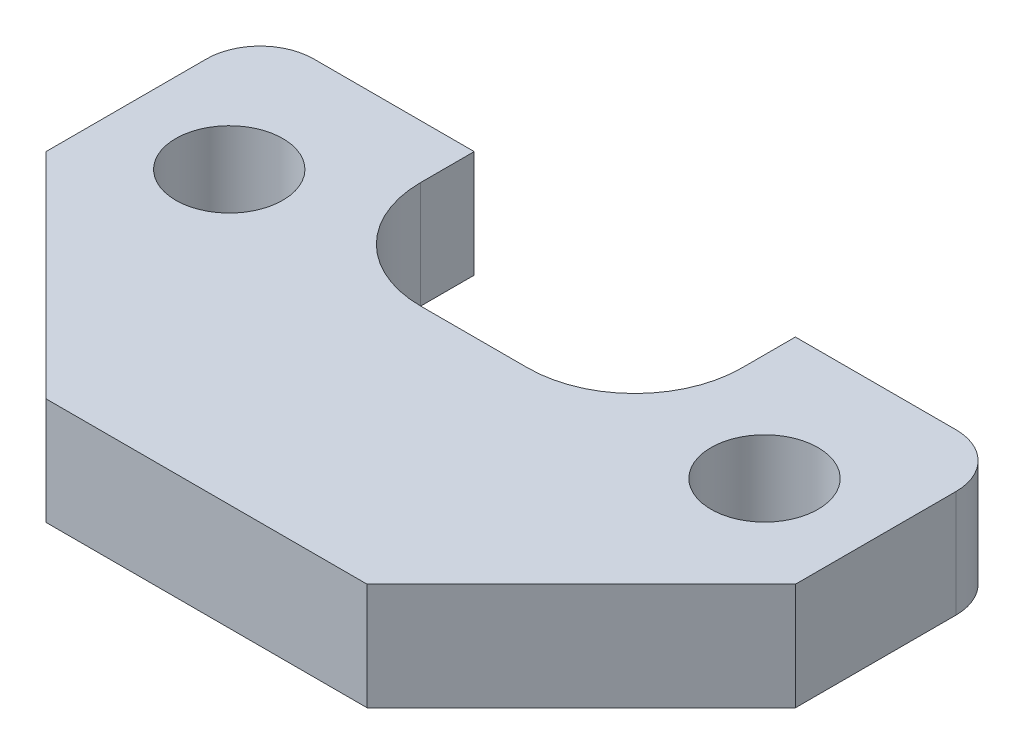
SolidWorks part; units mm, degrees
ref_plane "Front Plane" through (0, 0, 0) normal (0, 0, 1) x (1, 0, 0)
ref_plane "Top Plane" through (0, 0, 0) normal (0, 1, 0) x (1, 0, 0)
ref_plane "Right Plane" through (0, 0, 0) normal (1, 0, 0) x (0, 0, -1)
sketch "Sketch1" plane through (0, 0, 0) normal (0, 1, 0) x (1, 0, 0)
  line L0 (-30, 12.8823) -> (-15, 12.8823)
  line L1 (-15, 12.8823) -> (-15, 7.8823)
  line L8 (-15, -27.1177) -> (-35, -7.1177)
  line L9 (-35, -7.1177) -> (-35, 7.8823)
  line L10 (0, 67.1732) -> (0, -67.1732) construction
  line L11 (-5, -2.1177) -> (5, -2.1177)
  line L12 (-15, -27.1177) -> (15, -27.1177)
  line L13 (35, -7.1177) -> (35, 7.8823)
  line L14 (15, -27.1177) -> (35, -7.1177)
  line L15 (15, 12.8823) -> (15, 7.8823)
  line L16 (30, 12.8823) -> (15, 12.8823)
  circle A0 centre (-25, 0) radius 5
  arc A1 (-15, 7.8823) -> (-5, -2.1177) centre (-5, 7.8823) ccw
  circle A2 centre (25, 0) radius 5
  arc A3 (15, 7.8823) -> (5, -2.1177) centre (5, 7.8823) cw
  arc A4 (-30, 12.8823) -> (-35, 7.8823) centre (-30, 7.8823) ccw
  arc A5 (35, 7.8823) -> (30, 12.8823) centre (30, 7.8823) ccw
  point P2 (0, 0)
  point P3 (0, 0)
  point P7 (0, 0)
  point P13 (-1.1285, -52.8694)
  point P18 (-15, -2.1177)
  point P24 (0, -27.1177)
  point P25 (0, -2.1177)
  point P30 (-35, 12.8823)
  point P33 (35, 12.8823)
  dimension "D2" = 10
  dimension "D3" = 20
  dimension "D8" = 40
  dimension "D10" = 10
  dimension "D11" = 5
  dimension "D12" = 5
  dimension "D1" = 20
  dimension "D4" = 10
  dimension "D5" = 10
  dimension "D6" = 15
  dimension "D7" = 15
  dimension "D9" = 27.1177
extrude "Boss-Extrude2" add sketch "Sketch1" along normal blind 5 and the other way blind 5
